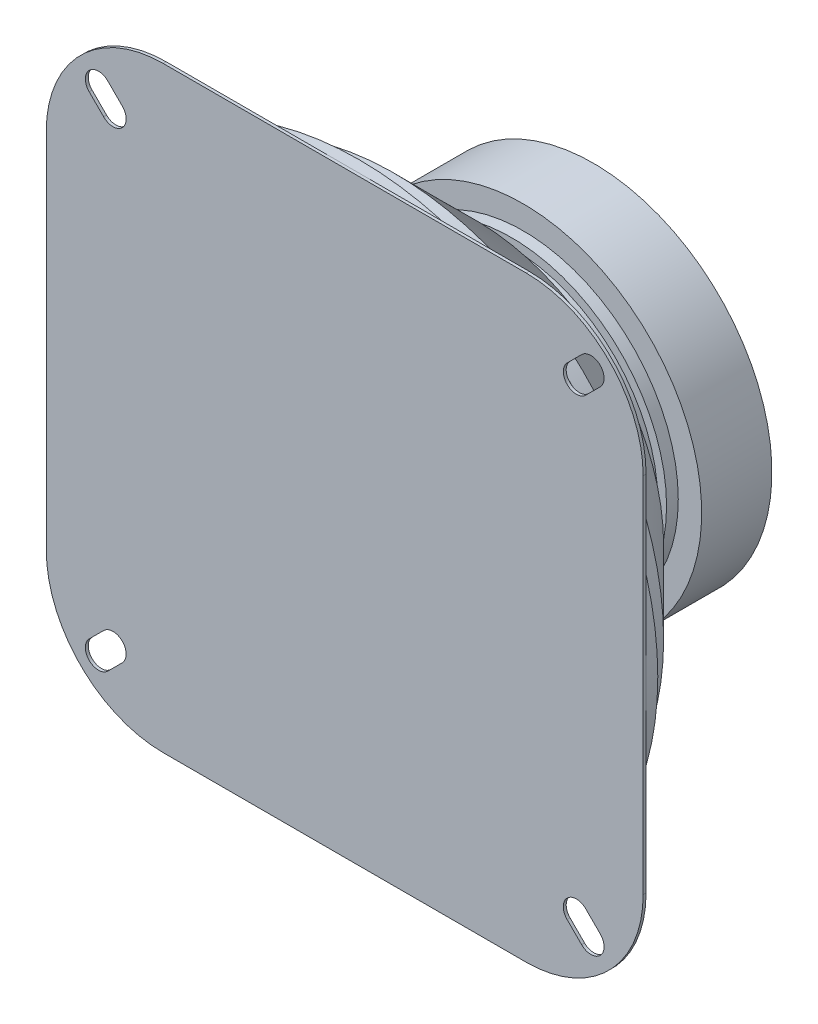
SolidWorks part; units mm, degrees
ref_plane "Plan de face" through (0, 0, 0) normal (0, 0, 1) x (1, 0, 0)
ref_plane "Plan de dessus" through (0, 0, 0) normal (0, 1, 0) x (1, 0, 0)
ref_plane "Plan de droite" through (0, 0, 0) normal (1, 0, 0) x (0, 0, -1)
sketch "Esquisse1" plane through (0, 0, 0) normal (0, 0, 1) x (1, 0, 0)
  circle A0 centre (0, 0) radius 26.5
  dimension "D1" = 53
extrude "Boss.-Extru.1" add sketch "Esquisse1" along normal blind 16
sketch "Esquisse4" plane through (0, 0, 16) normal (0, 0, 1) x (1, 0, 0)
  circle A0 centre (0, 0) radius 25
  dimension "D1" = 50
extrude "Boss.-Extru.2" add sketch "Esquisse4" along normal blind 6
sketch "Esquisse5" plane through (0, 0, 22) normal (0, 0, 1) x (1, 0, 0)
  circle A0 centre (0, 0) radius 46
  dimension "D1" = 92
extrude "Boss.-Extru.3" add sketch "Esquisse5" along normal blind 14
chamfer "Chanfrein1" distance 14 angle 45 1 edges at (46, 0, 22)
sketch "Esquisse6" plane through (0, 0, 36) normal (0, 0, 1) x (1, 0, 0)
  circle A0 centre (0, 0) radius 46
extrude "Boss.-Extru.4" add sketch "Esquisse6" along normal blind 6
sketch "Esquisse7" plane through (0, 0, 42) normal (0, 0, 1) x (1, 0, 0)
  circle A0 centre (0, 0) radius 51
  dimension "D1" = 102
extrude "Boss.-Extru.5" add sketch "Esquisse7" along normal blind 2
sketch "Esquisse8" plane through (0, 0, 44) normal (0, 0, 1) x (1, 0, 0)
  line L0 (-51, -51) -> (51, 51)
  line L1 (-31, 51) -> (31, 51)
  line L2 (-51, 31) -> (-51, -31)
  line L3 (-31, -51) -> (31, -51)
  line L4 (51, 31) -> (51, -31)
  line L5 (51, -51) -> (-51, 51)
  line L6 (-42.0729, -42.0729) -> (-39.598, -39.598) construction
  line L7 (-43.6638, -40.4819) -> (-41.189, -38.007)
  line L8 (-40.4819, -43.6638) -> (-38.007, -41.189)
  line L9 (-39.598, 39.598) -> (-42.0729, 42.0729) construction
  line L10 (-41.189, 38.007) -> (-43.6638, 40.4819)
  line L11 (-38.007, 41.189) -> (-40.4819, 43.6638)
  line L12 (39.598, 39.598) -> (42.0729, 42.0729) construction
  line L13 (38.007, 41.189) -> (40.4819, 43.6638)
  line L14 (41.189, 38.007) -> (43.6638, 40.4819)
  line L15 (39.598, -39.598) -> (42.0729, -42.0729) construction
  line L16 (41.189, -38.007) -> (43.6638, -40.4819)
  line L17 (38.007, -41.189) -> (40.4819, -43.6638)
  arc A0 (-31, -51) -> (-51, -31) centre (-31, -31) cw
  circle A1 centre (0, 0) radius 51
  arc A2 (-43.6638, -40.4819) -> (-40.4819, -43.6638) centre (-42.0729, -42.0729) ccw
  arc A3 (-38.007, -41.189) -> (-41.189, -38.007) centre (-39.598, -39.598) ccw
  arc A4 (-41.189, 38.007) -> (-38.007, 41.189) centre (-39.598, 39.598) ccw
  arc A5 (-40.4819, 43.6638) -> (-43.6638, 40.4819) centre (-42.0729, 42.0729) ccw
  arc A6 (38.007, 41.189) -> (41.189, 38.007) centre (39.598, 39.598) ccw
  arc A7 (43.6638, 40.4819) -> (40.4819, 43.6638) centre (42.0729, 42.0729) ccw
  arc A8 (41.189, -38.007) -> (38.007, -41.189) centre (39.598, -39.598) ccw
  arc A9 (40.4819, -43.6638) -> (43.6638, -40.4819) centre (42.0729, -42.0729) ccw
  arc A14 (31, -51) -> (51, -31) centre (31, -31) ccw
  arc A15 (51, 31) -> (31, 51) centre (31, 31) ccw
  arc A16 (-31, 51) -> (-51, 31) centre (-31, 31) ccw
  point P4 (-51, 0)
  point P5 (0, 51)
  point P11 (-40.8354, -40.8354)
  point P16 (-40.8354, 40.8354)
  point P23 (40.8354, 40.8354)
  point P30 (40.8354, -40.8354)
  point P37 (39.2444, -42.4264)
  point P38 (42.4264, -39.2444)
  point P39 (-42.4264, 39.2444)
  point P40 (-39.2444, 42.4264)
  point P41 (39.2444, 42.4264)
  circle M3 centre (0, 0) radius 51
  dimension "D3" = 51
  dimension "D17" = 20
  dimension "D1" = 102
  dimension "D2" = 4.5
  dimension "D4" = 51
  dimension "D5" = 3.5
  dimension "D6" = 3.5
  dimension "D7" = 3.5
  dimension "D8" = 3.5
  dimension "D9" = 4.5
  dimension "D10" = 4.5
  dimension "D11" = 4.5
  dimension "D13" = 56
  dimension "D14" = 56
  dimension "D15" = 56
  dimension "D16" = 56
extrude "Boss.-Extru.6" add sketch "Esquisse8" along normal blind 0.5 contours A3 L0 L2 A0 A2 L7 M3 | A3 L8 A2 L0 A0 L3 M3 | L5 L0 M3 | L3 A14 L5 A9 L17 A8 M3 | L5 A14 L4 A8 L16 A9 M3 | L5 L0 M3 | L4 A15 L0 A7 L14 A6 M3 | L0 A15 L1 A6 L13 A7 M3 | L5 L0 M3 | L1 A16 L5 A5 L11 A4 M3 | L5 A16 L2 A4 L10 A5 M3 | L0 L5 M3 region at (-46.2069, -30.1356, 44) region at (-30.1356, -46.2069, 44) region at (30.1356, -46.2069, 44) region at (0, -30.6108, 44) region at (-46.2069, 30.1356, 44) region at (-30.6108, 0, 44) region at (46.2069, -30.1356, 44) region at (30.6108, 0, 44) region at (0, 30.6108, 44) region at (-30.1356, 46.2069, 44) region at (46.2069, 30.1356, 44) region at (30.1356, 46.2069, 44)
sketch "Esquisse9" plane through (0, 0, 0) normal (0, 0, -1) x (-1, 0, 0)
  circle A0 centre (0, 0) radius 30.5
  dimension "D1" = 61
extrude "Boss.-Extru.7" add sketch "Esquisse9" against normal blind 14 separate body
sketch "Esquisse10" plane through (0, 0, 0) normal (0, 0, -1) x (-1, 0, 0)
  circle A0 centre (0, 0) radius 26.5
  circle A1 centre (0, 0) radius 30.5
extrude "Enlèv. mat.-Extru.1" cut sketch "Esquisse10" against normal blind 2
